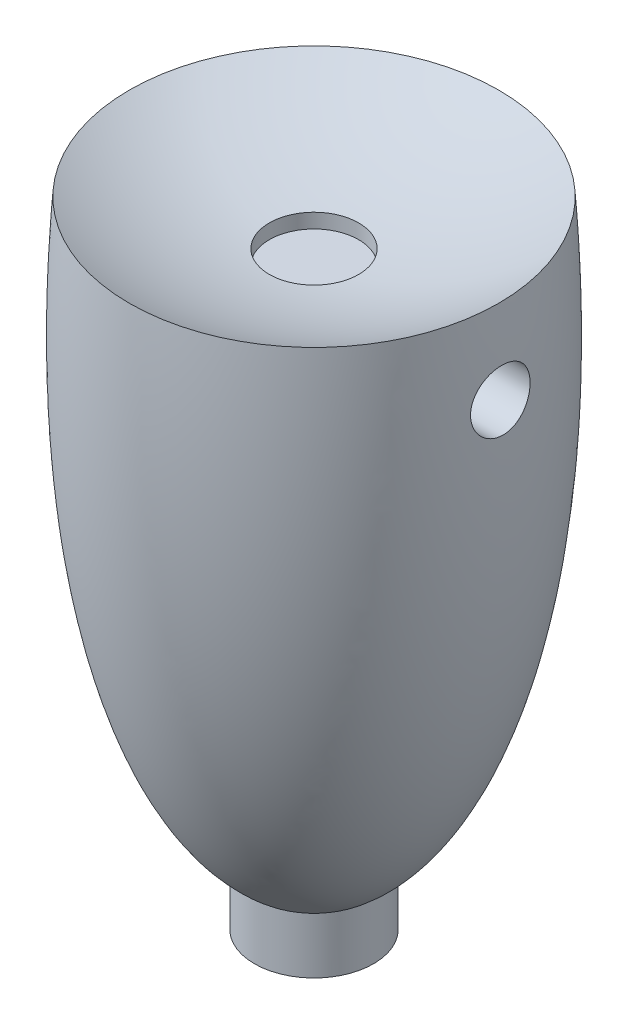
SolidWorks part; units mm, degrees
ref_plane "Front" through (0, 0, 0) normal (0, 0, 1) x (1, 0, 0)
ref_plane "Top" through (0, 0, 0) normal (0, 1, 0) x (1, 0, 0)
ref_plane "Right" through (0, 0, 0) normal (1, 0, 0) x (0, 0, -1)
sketch "Sketch2" plane through (0, 0, 0) normal (0, 0, 1) x (1, 0, 0)
  line L0 (0, 0) -> (3.1, 0)
  line L1 (1.6775, 0) -> (-1.6775, 0) construction
  line L2 (0, -10.152) -> (0, 0)
  line L3 (0, -6.7789) -> (0, 6.7789) construction
  spline S0 degree 3 poles (0, -10.152) (2.1776, -9.8573) (3.5151, -5.7935) (3.1, 0) knots 0 0 0 0 1 1 1 1
  point P6 (0, -10.2575)
  point P7 (3.05, 0)
  point P10 (3.05, 0)
  point P11 (3.05, 0)
  point P12 (3.05, 0)
  point P13 (3.4155, 0)
  point P14 (3.1443, 0.0309)
  point P15 (3.4595, 0.0383)
  point P16 (0, -10.1284)
  dimension "D1" = 3.1
  dimension "D2" = 10.152
revolve "Revolve2" add sketch "Sketch2" angle 360 about L2
dome "Dome2" faces to dome 1 distance 0.8 reverse direction yes elliptical dome no face at (0, 0, -3.1) parameters "D1"=0.8
sketch "Sketch3" plane through (0, 0, 0) normal (1, 0, 0) x (0, 0, -1)
  line L0 (0, 3.6383) -> (0, -3.6383) construction
  spline S0 degree 3 poles (-3.1, 0) (-3.5151, -5.7935) (-2.1776, -9.8573) (0, -10.152) knots 0 0 0 0 1 1 1 1 construction
  point P0 (0, -10.152)
  point P6 (0, 0)
ref_plane "Plane1" through (0, -10.152, 0) normal (0, 1, 0) x (1, 0, 0)
sketch "Sketch5" plane through (0, 0, 0) normal (0, 0, 1) x (1, 0, 0)
  spline S0 degree 3 poles (0, -10.152) (2.1776, -9.8573) (3.5151, -5.7935) (3.1, 0) knots 0 0 0 0 1 1 1 1 construction
  point P0 (3.167, -1.3773)
ref_plane "Plane2" through (3.167, 0, 0) normal (1, 0, 0) x (0, 0, -1)
sketch "Sketch6" plane through (3.167, 0, 0) normal (1, 0, 0) x (0, 0, -1)
  circle A0 centre (0, -1.3773) radius 0.5
extrude "Cut-Extrude2" cut sketch "Sketch6" along normal blind 1 and the other way blind 1
mirror "Mirror1" about plane through (0, 0, 0) normal (1, 0, 0) of "Cut-Extrude2"
sketch "Sketch7" plane through (0, 0, 0) normal (0, 1, 0) x (1, 0, 0)
  circle A0 centre (0, 0) radius 0.75
  dimension "D1" = 1.5
extrude "Cut-Extrude3" cut sketch "Sketch7" against normal blind 1
sketch "Sketch9" plane through (0, -10.152, 0) normal (0, 1, 0) x (1, 0, 0)
  circle A0 centre (0, 0) radius 1
  circle A1 centre (0, 0) radius 0.45
  dimension "D1" = 2
  dimension "D2" = 0.9
extrude "Boss-Extrude1" add sketch "Sketch9" along normal up to surface and the other way blind 0.5
